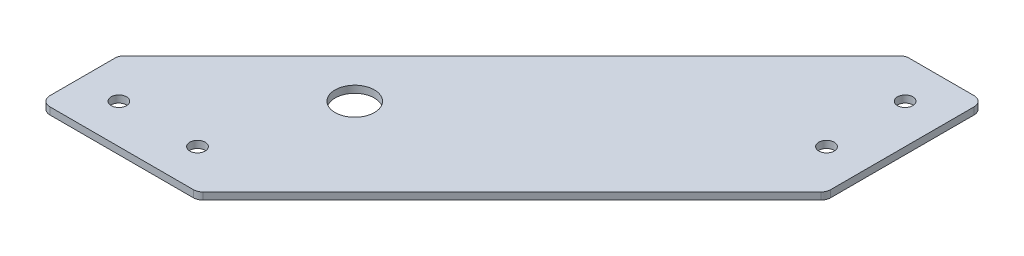
SolidWorks part; units mm, degrees
ref_plane "Front Plane" through (0, 0, 0) normal (0, 0, 1) x (1, 0, 0)
ref_plane "Top Plane" through (0, 0, 0) normal (0, 1, 0) x (1, 0, 0)
ref_plane "Right Plane" through (0, 0, 0) normal (1, 0, 0) x (0, 0, -1)
sketch "Sketch1" plane through (0, 0, 0) normal (0, 1, 0) x (1, 0, 0)
  line L0 (0, 0) -> (0, 152.4)
  line L1 (0, 152.4) -> (-25.4, 152.4)
  line L2 (-25.4, 152.4) -> (-152.4, 25.4)
  line L3 (-152.4, 25.4) -> (-152.4, 0)
  line L4 (-152.4, 0) -> (0, 0)
  circle A0 centre (-12.7, 12.7) radius 2.4892
  circle A1 centre (-38.1, 12.7) radius 2.4892
  circle A2 centre (-63.5, 12.7) radius 2.4892
  circle A3 centre (-88.9, 12.7) radius 2.4892
  circle A4 centre (-114.3, 12.7) radius 2.4892
  circle A5 centre (-12.7, 38.1) radius 2.4892
  circle A6 centre (-12.7, 63.5) radius 2.4892
  circle A7 centre (-12.7, 88.9) radius 2.4892
  circle A8 centre (-12.7, 114.3) radius 2.4892
  circle A9 centre (-139.7, 12.7) radius 2.4892
  circle A13 centre (-12.7, 139.7) radius 2.4892
  circle A17 centre (-101.6, 50.8) radius 6.35
  dimension "D4" = 12.7
  dimension "D5" = 12.7
  dimension "D8" = 12.7
  dimension "D1" = 152.4
  dimension "D2" = 25.4
  dimension "D3" = 152.4
  dimension "D9" = 101.6
  dimension "D10" = 50.8
  dimension "D11" = 25.4
  dimension "D6" = 6
  dimension "D7" = 6
extrude "Boss-Extrude2" add sketch "Sketch1" along normal mid plane 2.286
sketch "Sketch2" plane through (0, 1.143, 0) normal (0, 1, 0) x (1, 0, 0)
  line L0 (0, 0) -> (0, 101.6)
  line L1 (0, 0) -> (0, 152.4) construction
  line L2 (0, 101.6) -> (-101.6, 0)
  line L3 (-152.4, 0) -> (0, 0) construction
  line L4 (-101.6, 0) -> (0, 0)
  dimension "D1" = 45
  dimension "D2" = 101.6
  dimension "D3" = 101.6
extrude "Cut-Extrude1" cut sketch "Sketch2" against normal through all
sketch "Sketch3" plane through (0, 1.143, 0) normal (0, 1, 0) x (1, 0, 0)
  line L0 (-101.6, 0) -> (-101.6, 15.1204)
  line L1 (-101.6, 15.1204) -> (-15.6123, 101.1081)
  line L2 (-15.6123, 101.1081) -> (0, 101.6)
  line L3 (0, 101.6) -> (-101.6, 0)
extrude "Boss-Extrude3" add sketch "Sketch3" against normal blind 2.286
fillet "Fillet3" radius 3.175 6 edges at (-152.4, 0, 0) (-25.4, 0, -152.4) (0, 0, -152.4) (0, 0, -101.6) (-101.6, 0, 0) (-152.4, 0, -25.4)
ref_plane "Plane1" through (-152.4, 1.143, -24.0849) normal (0, 0, 1) x (1, 0, 0)
sketch "Sketch5" plane through (0, 1.143, 0) normal (0, 1, 0) x (1, 0, 0)
  line L0 (0, 0) -> (0, 152.4) construction
  line L1 (0, 152.4) -> (-152.4, 152.4) construction
  line L2 (0, 0) -> (-152.4, 0) construction
  line L3 (-152.4, 0) -> (-152.4, 152.4) construction
  dimension "D1" = 152.4
  dimension "D2" = 152.4
equation "\"0.09inin\"=0.1"
